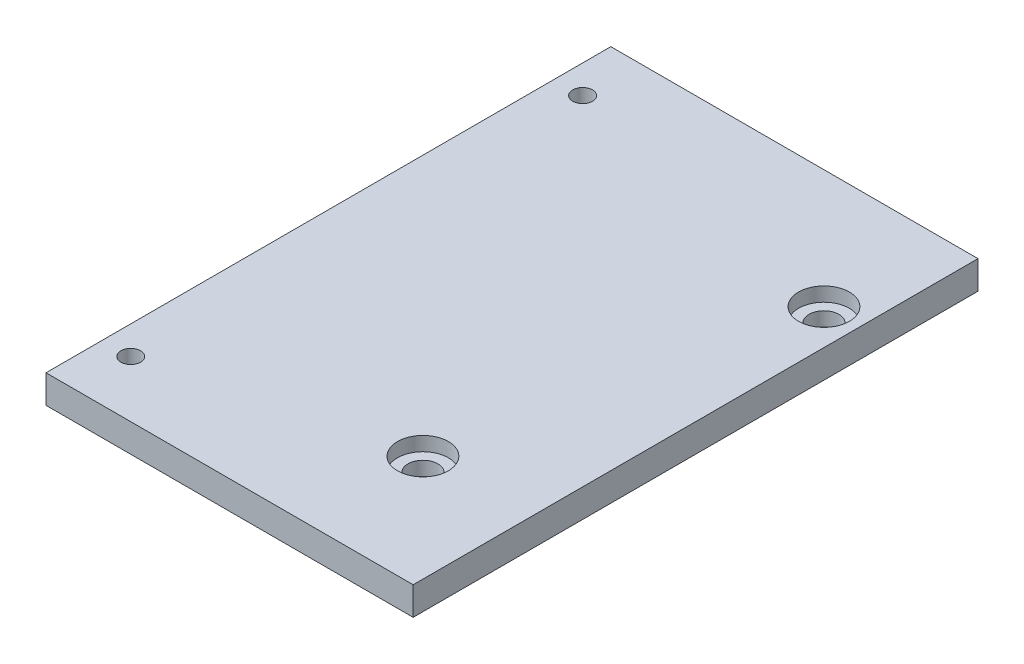
SolidWorks part; units mm, degrees
ref_plane "Front Plane" through (0, 0, 0) normal (0, 0, 1) x (1, 0, 0)
ref_plane "Top Plane" through (0, 0, 0) normal (0, 1, 0) x (1, 0, 0)
ref_plane "Right Plane" through (0, 0, 0) normal (1, 0, 0) x (0, 0, -1)
sketch "Sketch2" plane through (0, 0, 0) normal (0, 1, 0) x (1, 0, 0)
  line L1 (-32.5, 50) -> (32.5, 50)
  line L2 (-32.5, 50) -> (-32.5, -50)
  line L3 (-32.5, -50) -> (32.5, -50)
  line L4 (32.5, 50) -> (32.5, -50)
  line L5 (-32.5, 50) -> (32.5, -50) construction
  line L6 (-32.5, -50) -> (32.5, 50) construction
  circle A0 centre (-27.5, 40) radius 1.75
  circle A1 centre (-27.5, -40) radius 1.75
  circle A2 centre (26.23, 29) radius 2.65
  circle A3 centre (13.65, -29.42) radius 2.65
  point P0 (0, 0)
  dimension "D3" = 3.5
  dimension "D4" = 5
  dimension "D8" = 5.3
  dimension "D9" = 5.3
  dimension "D1" = 65
  dimension "D2" = 100
  dimension "D5" = 5
  dimension "D6" = 10
  dimension "D7" = 10
  dimension "D10" = 18.85
  dimension "D11" = 20.58
  dimension "D12" = 6.27
  dimension "D13" = 21
extrude "Boss-Extrude1" add sketch "Sketch2" along normal blind 5
sketch "Sketch3" plane through (0, 5, 0) normal (0, 1, 0) x (1, 0, 0)
  circle A0 centre (26.23, 29) radius 4.5
  circle A1 centre (13.65, -29.42) radius 4.5
  dimension "D1" = 9
  dimension "D2" = 9
extrude "Cut-Extrude1" cut sketch "Sketch3" against normal blind 2.5
